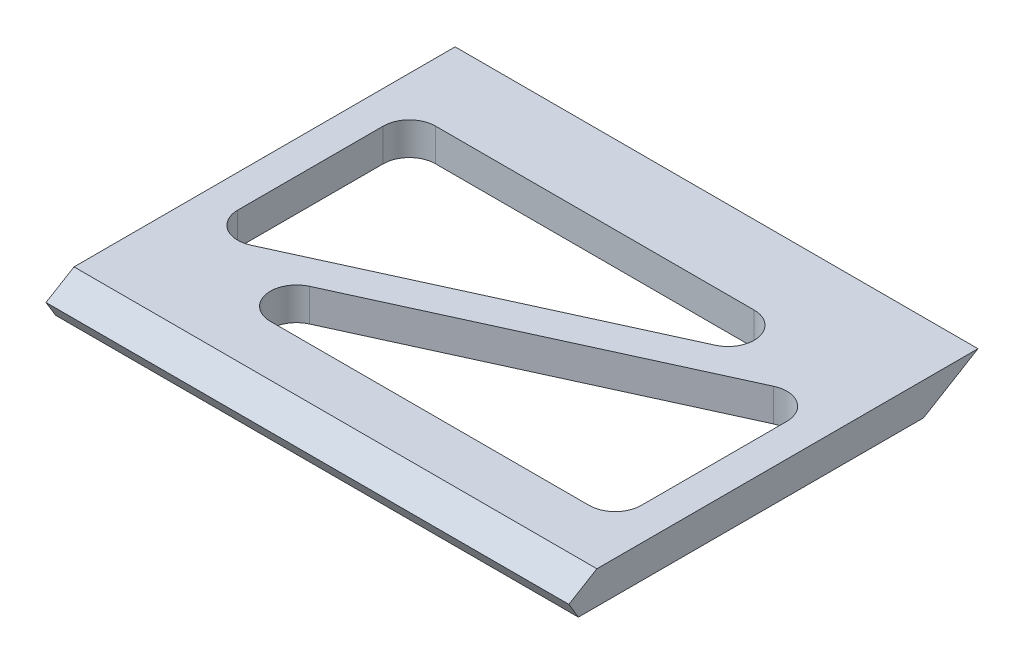
SolidWorks part; units mm, degrees
material "Balsa"
ref_plane "Front Plane" through (0, 0, 0) normal (0, 0, 1) x (1, 0, 0)
ref_plane "Top Plane" through (0, 0, 0) normal (0, 1, 0) x (1, 0, 0)
ref_plane "Right Plane" through (0, 0, 0) normal (1, 0, 0) x (0, 0, -1)
sketch "Sketch3" plane through (71.1933, 0, 0) normal (1, 0, 0) x (0, 0, -1)
  line L0 (56.968, 6.35) -> (46.3846, 0)
  line L1 (46.3846, 0) -> (-20.6804, 0)
  line L2 (-20.6804, 0) -> (-22.5302, 3.083)
  line L3 (-22.5302, 3.083) -> (-29.7177, 15.0621) construction
  line L4 (56.968, 6.35) -> (63.7199, 10.4011) construction
  line L6 (-22.5302, 3.083) -> (-17.0851, 6.35)
  line L7 (-17.0851, 6.35) -> (56.968, 6.35)
extrude "Boss-Extrude2" add sketch "Sketch3" against normal up to surface (101.6 mm away)
sketch "Sketch4" plane through (0, 6.35, 0) normal (0, 1, 0) x (1, 0, 0)
  line L0 (-30.4067, -17.0851) -> (-30.4067, 56.968) construction
  line L1 (-18.9767, 41.728) -> (42.949, 41.728)
  line L2 (-24.0567, 36.648) -> (-24.0567, 8.3732)
  line L3 (-2.1624, -7.1791) -> (59.7633, -7.1791)
  line L4 (64.8433, 26.1757) -> (64.8433, -2.0991)
  line L5 (-30.4067, 56.968) -> (71.1933, 56.968) construction
  line L6 (71.1933, 56.968) -> (71.1933, -17.0851) construction
  line L7 (-30.4067, -17.0851) -> (71.1933, -17.0851) construction
  line L8 (-16.8668, 3.7521) -> (45.0589, 32.0269)
  line L9 (-4.2724, 2.522) -> (57.6533, 30.7968)
  line L10 (-29.6117, -5.5575) -> (68.6464, 39.3064)
  arc A0 (-4.2724, 2.522) -> (-2.1624, -7.1791) centre (-2.1624, -2.0991) ccw
  arc A1 (59.7633, -7.1791) -> (64.8433, -2.0991) centre (59.7633, -2.0991) ccw
  arc A2 (57.6533, 30.7968) -> (64.8433, 26.1757) centre (59.7633, 26.1757) cw
  arc A3 (45.0589, 32.0269) -> (42.949, 41.728) centre (42.949, 36.648) ccw
  arc A4 (-18.9767, 41.728) -> (-24.0567, 36.648) centre (-18.9767, 36.648) ccw
  arc A5 (-16.8668, 3.7521) -> (-24.0567, 8.3732) centre (-18.9767, 8.3732) cw
  dimension "D7" = 5.08
  dimension "D1" = 6.35
  dimension "D2" = 15.24
  dimension "D3" = 6.35
  dimension "D4" = 9.906
  dimension "D5" = 3.175
  dimension "D6" = 3.175
extrude "Cut-Extrude1" cut sketch "Sketch4" against normal up to surface (6.35 mm away) contours A5 L8 A3 L1 A4 L2 | A2 L9 A0 L3 A1 L4 region at (4.1335, 6.35, -27.6167) region at (36.6531, 6.35, -6.9321) up to face at (20.3933, 0, -12.8521)
